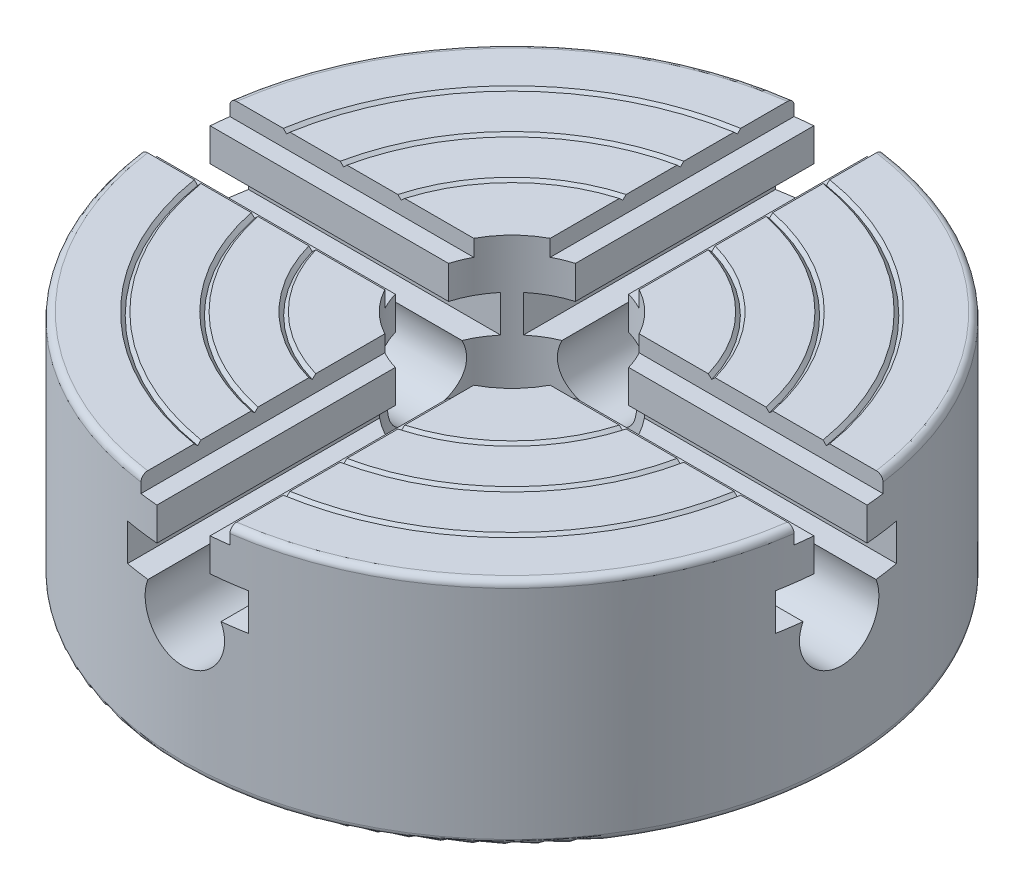
SolidWorks part; units mm, degrees
material "AISI 4340 Steel, normalized"
ref_plane "Front Plane" through (0, 0, 0) normal (0, 0, 1) x (1, 0, 0)
ref_plane "Top Plane" through (0, 0, 0) normal (0, 1, 0) x (1, 0, 0)
ref_plane "Right Plane" through (0, 0, 0) normal (1, 0, 0) x (0, 0, -1)
sketch "Sketch1" plane through (0, 0, 0) normal (0, 1, 0) x (1, 0, 0)
  circle A0 centre (0, 0) radius 100
  dimension "D1" = 200
extrude "Boss-Extrude1" add sketch "Sketch1" along normal blind 70
sketch "Sketch2" plane through (0, 70, 0) normal (0, 1, 0) x (1, 0, 0)
  circle A0 centre (0, 0) radius 49 construction
  circle A1 centre (0, 0) radius 66 construction
  circle A2 centre (0, 0) radius 83 construction
  circle A3 centre (0, 0) radius 50
  circle A4 centre (0, 0) radius 67
  circle A5 centre (0, 0) radius 84
  circle A6 centre (0, 0) radius 48
  circle A7 centre (0, 0) radius 65
  circle A8 centre (0, 0) radius 82
  dimension "D1" = 166
  dimension "D2" = 132
  dimension "D3" = 98
  dimension "D4" = 1
  dimension "D5" = 1
extrude "Cut-Extrude1" cut sketch "Sketch2" against normal blind 1 draft 45 contours A3 A6 | A4 A7 | A5 A8 region at (-48.5858, 70, 0) region at (-65.105, 70, 0) region at (-83.7624, 70, 0)
sketch "Sketch3" plane through (0, 70, 0) normal (0, 1, 0) x (1, 0, 0)
  circle A0 centre (0, 0) radius 28.5
  dimension "D1" = 57
extrude "Cut-Extrude2" cut sketch "Sketch3" against normal through all
sketch "Sketch6" plane through (0, 0, 0) normal (1, 0, 0) x (0, 0, -1)
  line L0 (0, 87.3867) -> (0, -17.3867) construction
  line L1 (13.5, 70) -> (-13.5, 70)
  line L2 (100, 70) -> (-100, 70) construction
  line L3 (28.5, 70) -> (-28.5, 70) construction
  line L4 (-13.5, 70) -> (-13.5, 65)
  line L5 (-13.5, 65) -> (-8.0797, 65)
  line L6 (-8.0797, 65) -> (-8.0797, 55)
  line L7 (-8.0797, 55) -> (-18.3497, 55)
  line L8 (-18.3497, 55) -> (-18.3497, 43.8)
  line L9 (-18.3497, 43.8) -> (-11.0743, 43.8)
  line L10 (48, 70) -> (-48, 70) construction
  line L11 (18.3497, 43.8) -> (11.0743, 43.8)
  line L12 (18.3497, 55) -> (18.3497, 43.8)
  line L13 (8.0797, 55) -> (18.3497, 55)
  line L14 (8.0797, 65) -> (8.0797, 55)
  line L15 (13.5, 65) -> (8.0797, 65)
  line L16 (13.5, 70) -> (13.5, 65)
  arc A0 (-11.0743, 43.8) -> (11.0743, 43.8) centre (0, 39.05) ccw
  point P25 (0, 70)
  dimension "D5" = 24.1
  dimension "D1" = 13.5
  dimension "D2" = 5
  dimension "D3" = 15
  dimension "D4" = 26.2
  dimension "D6" = 4.75
extrude "Cut-Extrude3" cut sketch "Sketch6" along normal through all
pattern_circular "CirPattern1" count 4 over 360 about axis through (0, 0, 0) along (0, 1, 0) of "Cut-Extrude3" reverse direction yes
fillet "Fillet1" radius 2 5 edges at (-70.7107, 70, 70.7107) (-70.7107, 70, -70.7107) (70.7107, 70, -70.7107) (70.7107, 70, 70.7107) (0, 0, 100)
sketch "Sketch42" plane through (0, 0, 0) normal (0, -1, 0) x (-1, 0, 0)
  circle A0 centre (0, -60) radius 13
  dimension "D1" = 26
  dimension "D2" = 60
extrude "Cut-Extrude11" cut sketch "Sketch42" against normal blind 49
pattern_circular "CirPattern3" count 4 over 360 about axis through (0, 70, 0) along (0, -1, 0) of "Cut-Extrude11" reverse direction yes
sketch "Sketch43" plane through (0, 0, 0) normal (0, -1, 0) x (1, 0, 0)
  circle A0 centre (0, 0) radius 87.5
  circle A1 centre (0, 0) radius 55
  dimension "D1" = 175
  dimension "D2" = 110
extrude "Cut-Extrude12" cut sketch "Sketch43" against normal blind 1 draft 45
sketch "Sketch44" plane through (0, 0, 0) normal (0, -1, 0) x (1, 0, 0)
  line L0 (0, 104.9201) -> (0, -21.6297) construction
  line L1 (0, 0) -> (-28.9914, -28.9914) construction
  circle A0 centre (-28.9914, -28.9914) radius 8
  dimension "D1" = 16
  dimension "D2" = 41
  dimension "D3" = 225
extrude "Cut-Extrude13" cut sketch "Sketch44" against normal blind 10
sketch "Sketch45" plane through (0, 0, 0) normal (0, -1, 0) x (1, 0, 0)
  circle A0 centre (-34.2471, -18.7626) radius 5.5
  circle A3 centre (-28.9914, -28.9914) radius 8 construction
  dimension "D1" = 11
  dimension "D2" = 39.05
  dimension "D3" = 11.5
extrude "Cut-Extrude14" cut sketch "Sketch45" against normal blind 7
hole_wizard "M10x1.0 Tapped Hole5" positions "Sketch48" profile "Sketch49" tap size "M10x1.0" standard "ANSI Metric"
sketch "Sketch48" plane through (0, 10, 0) normal (0, -1, 0) x (-1, 0, 0)
  point P0 (28.9914, 28.9914)
cosmetic thread "Hole Thread4" parameters "D1"=20, "D2"=10
sketch "Sketch49" plane through (-28.9914, 10, -28.9914) normal (1, 0, 0) x (0, 0, -1)
  line L0 (0, 0) -> (0, 23)
  line L1 (0, 23) -> (4.5, 20.2961)
  line L2 (4.5, 20.2961) -> (4.5, 0)
  line L5 (4.5, 0) -> (0, 0)
  line L10 (0, 23) -> (-4.5, 20.2961) construction
  line L11 (0, -6.35) -> (0, 107.95) construction
  dimension "Tap Drill Dia." = 9
  dimension "Tap Drill Depth" = 23
  dimension "Drill Angle" = 118
hole_wizard "M6x1.0 Tapped Hole8" positions "Sketch50" profile "Sketch51" tap size "M6x1.0" standard "ANSI Metric"
sketch "Sketch50" plane through (0, 7, 0) normal (0, -1, 0) x (-1, 0, 0)
  point P0 (34.2471, 18.7626)
sketch "Sketch51" plane through (-34.2471, 7, -18.7626) normal (1, 0, 0) x (0, 0, -1)
  line L0 (0, 0) -> (0, 20)
  line L1 (0, 20) -> (2.5, 18.4978)
  line L2 (2.5, 18.4978) -> (2.5, 0)
  line L5 (2.5, 0) -> (0, 0)
  line L10 (0, 20) -> (-2.5, 18.4978) construction
  line L11 (0, -6.35) -> (0, 107.95) construction
  dimension "Tap Drill Dia." = 5
  dimension "Tap Drill Depth" = 20
  dimension "Drill Angle" = 118
cosmetic thread "Hole Thread5" parameters "D1"=12, "D2"=6
pattern_circular "CirPattern59" count 3 over 360 about axis through (0, 0, 0) along (0, 1, 0) of "M6x1.0 Tapped Hole8", "Cut-Extrude13", "Cut-Extrude14", "M10x1.0 Tapped Hole5"
cosmetic thread "Hole Thread12" parameters "D1"=20, "D2"=10
cosmetic thread "Hole Thread13" parameters "D1"=12, "D2"=6
cosmetic thread "Hole Thread14" parameters "D1"=12, "D2"=6
cosmetic thread "Hole Thread15" parameters "D1"=20, "D2"=10
sketch "Sketch52" plane through (0, 0, 0) normal (0, -1, 0) x (1, 0, 0)
  circle A0 centre (0, 0) radius 31.75
  dimension "63.5" = 63.5
extrude "Cut-Extrude15" cut sketch "Sketch52" against normal blind 11.11 draft 7
chamfer "Chamfer1" distance 1 angle 45 1 edges at (0, 0, -31.75) first distance on face at (0, 0, -31.75)
fillet "Fillet2" radius 0.5 1 edges at (0, 11.11, -30.3859)
